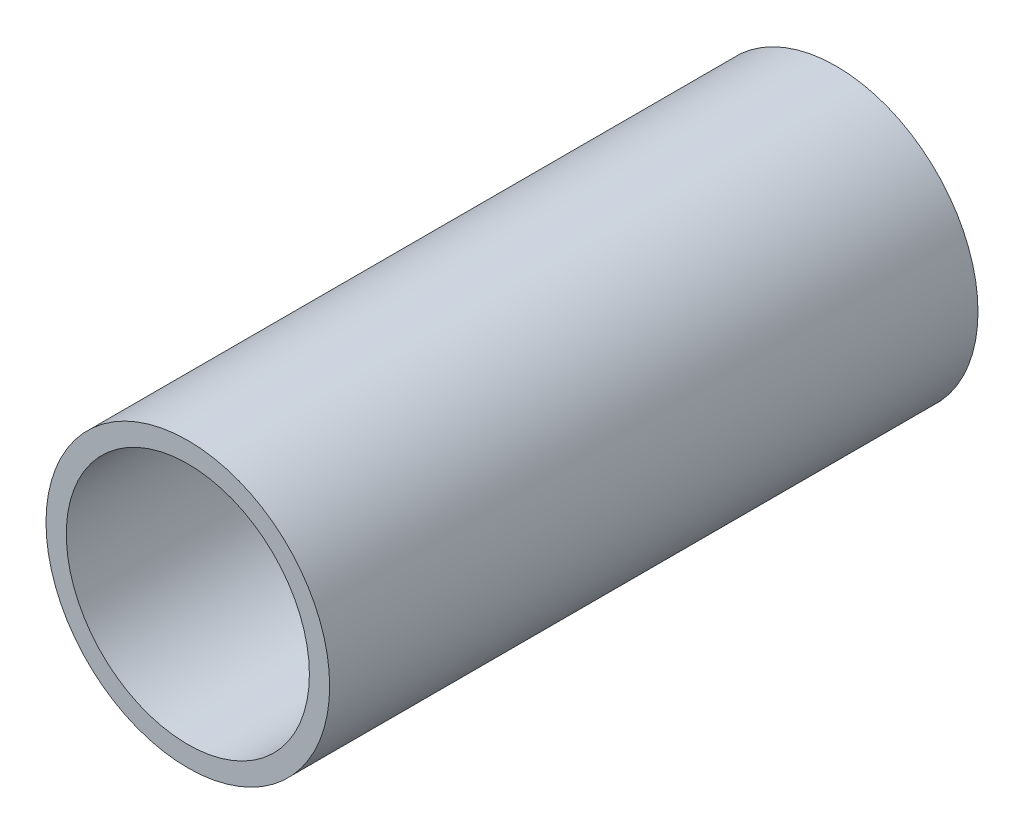
SolidWorks part; units mm, degrees
material "1060 Alloy"
ref_plane "Front Plane" through (0, 0, 0) normal (0, 0, 1) x (1, 0, 0)
ref_plane "Top Plane" through (0, 0, 0) normal (0, 1, 0) x (1, 0, 0)
ref_plane "Right Plane" through (0, 0, 0) normal (1, 0, 0) x (0, 0, -1)
sketch "Sketch1" plane through (0, 0, 0) normal (0, 0, 1) x (1, 0, 0)
  circle A0 centre (0, 0) radius 12.7
  circle A1 centre (0, 0) radius 44.45
  circle A2 centre (0, 0) radius 38.1
  dimension "D1" = 25.4
  dimension "D2" = 88.9
  dimension "D3" = 76.2
extrude "Boss-Extrude1" add sketch "Sketch1" along normal mid plane 203.2 contours A1 A2 region at (-43.1928, 0, 0)
extrude "Boss-Extrude2" add sketch "Sketch1<3>" along normal mid plane 50.8 contours A2 A0 region at (-37.0224, 0, 0)
sketch "Sketch1<3>" plane through (0, 0, 0) normal (0, 0, 1) x (1, 0, 0) same geometry as "Sketch1"
